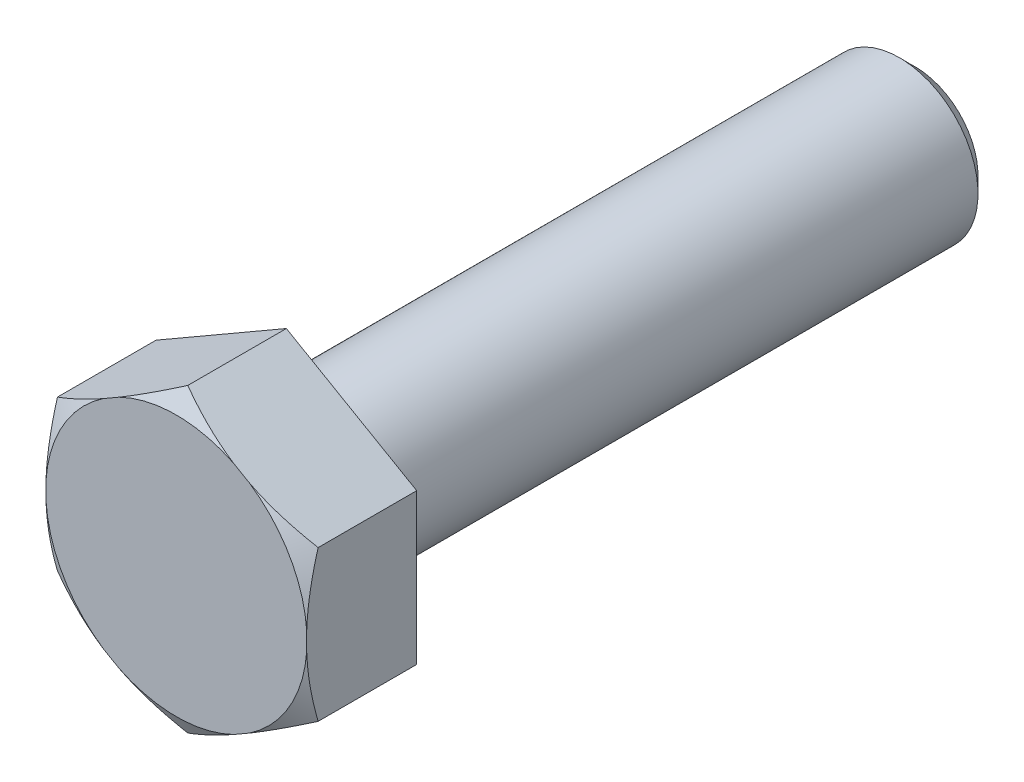
SolidWorks part; units mm, degrees
material "Простая углеродистая сталь"
ref_plane "Спереди" through (0, 0, 0) normal (0, 0, 1) x (1, 0, 0)
ref_plane "Сверху" through (0, 0, 0) normal (0, 1, 0) x (1, 0, 0)
ref_plane "Справа" through (0, 0, 0) normal (1, 0, 0) x (0, 0, -1)
sketch "Эскиз1" plane through (0, 0, 0) normal (0, 1, 0) x (1, 0, 0)
  line L0 (0, 0) -> (-4, 0)
  line L1 (-4, 0) -> (-4, 2.8)
  line L2 (-4, 2.8) -> (-2, 2.8)
  line L3 (-2, 2.8) -> (-2, 18.8)
  line L4 (-2, 18.8) -> (0, 18.8)
  line L5 (0, 18.8) -> (0, 0)
  dimension "D1" = 4
  dimension "D2" = 2.8
  dimension "D3" = 16
  dimension "D4" = 2
revolve "Повернуть1" add sketch "Эскиз1" angle 360 about L5
sketch "Эскиз2" plane through (0, 0, 0) normal (0, 0, 1) x (1, 0, 0)
  line L1 (0, 3.83) -> (-3.3169, 1.915)
  line L2 (-3.3169, 1.915) -> (-3.3169, -1.915)
  line L3 (-3.3169, -1.915) -> (0, -3.83)
  line L4 (0, -3.83) -> (3.3169, -1.915)
  line L5 (3.3169, -1.915) -> (3.3169, 1.915)
  line L6 (3.3169, 1.915) -> (0, 3.83)
  circle A0 centre (0, 0) radius 3.3169 construction
  dimension "D1" = 7.66
extrude "Вырез-Вытянуть1" cut sketch "Эскиз2" against normal up to surface (2.8 mm away) flip side to cut up to face at (-4, 0, -2.8)
sketch "Эскиз3" plane through (0, 0, 0) normal (1, 0, 0) x (0, 0, -1)
  line L1 (0, 0) -> (-50000, 0) construction
  line L3 (0, 3.83) -> (0.2916, 3.83)
  line L5 (2.8, 3.83) -> (0, 3.83) construction
  line L12 (0.2916, 3.83) -> (0, 3.325)
  line L13 (0, 1.915) -> (0, 3.83) construction
  line L14 (0, 3.325) -> (0, 3.83)
  dimension "D1" = 30
  dimension "D2" = 3.325
revolve "Вырез-Повернуть1" cut sketch "Эскиз3" angle 360 about L1
chamfer "Фаска1" distance 0.4 angle 45 1 edges at (-2, 0, -18.8)
fillet "Скругление1" radius 0.4 1 edges at (-2, 0, -2.8)
